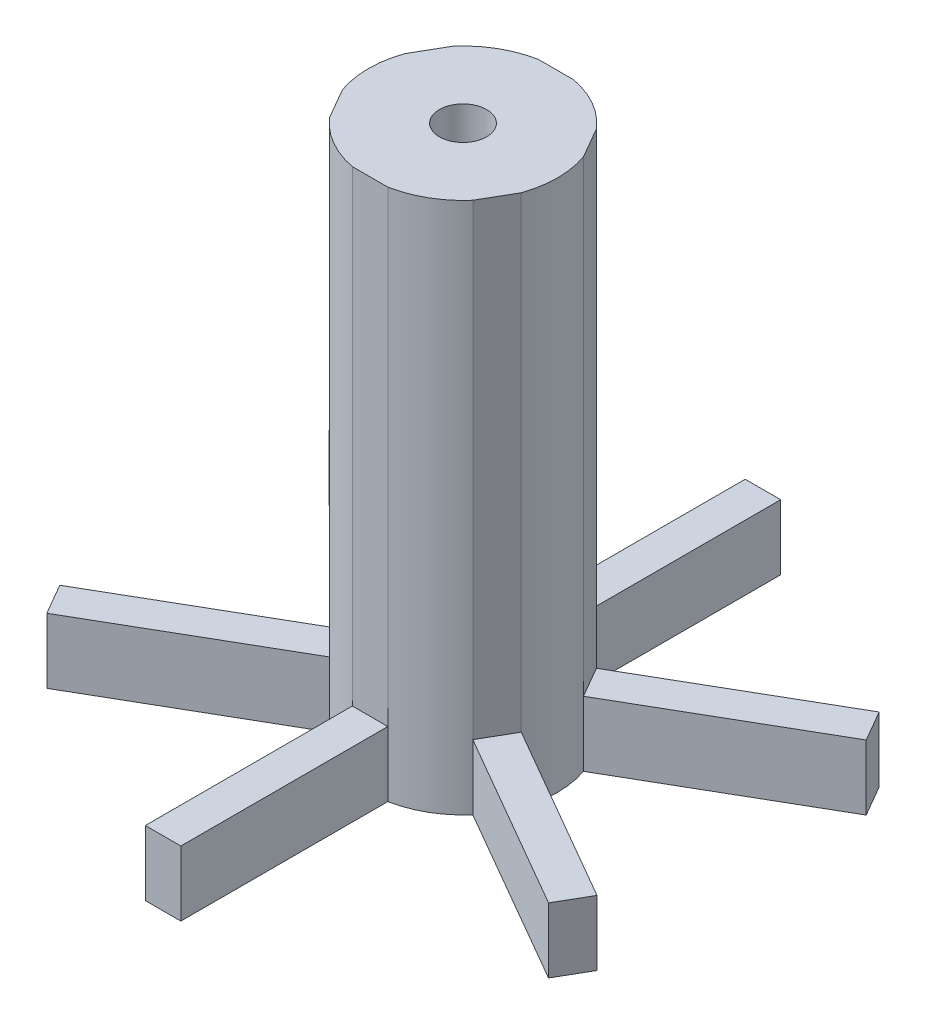
SolidWorks part; units mm, degrees
ref_plane "Front Plane" through (0, 0, 0) normal (0, 0, 1) x (1, 0, 0)
ref_plane "Top Plane" through (0, 0, 0) normal (0, 1, 0) x (1, 0, 0)
ref_plane "Right Plane" through (0, 0, 0) normal (1, 0, 0) x (0, 0, -1)
sketch "Sketch1" plane through (0, 0, 0) normal (0, 1, 0) x (1, 0, 0)
  line L24 (-1.5, -7.8581) -> (1.5, -7.8581)
  line L25 (1.5, -7.8581) -> (1.5, -25.3581)
  line L26 (1.5, -25.3581) -> (-1.5, -25.3581)
  line L27 (-1.5, -25.3581) -> (-1.5, -7.8581)
  line L28 (-22.7108, -11.38) -> (-7.5553, -2.63)
  line L29 (-7.5553, -2.63) -> (-6.0553, -5.2281)
  line L30 (-6.0553, -5.2281) -> (-21.2108, -13.9781)
  line L31 (-21.2108, -13.9781) -> (-22.7108, -11.38)
  line L32 (-21.2108, 13.9781) -> (-6.0553, 5.2281)
  line L33 (-6.0553, 5.2281) -> (-7.5553, 2.63)
  line L34 (-7.5553, 2.63) -> (-22.7108, 11.38)
  line L35 (-22.7108, 11.38) -> (-21.2108, 13.9781)
  line L36 (1.5, 25.3581) -> (1.5, 7.8581)
  line L37 (1.5, 7.8581) -> (-1.5, 7.8581)
  line L38 (-1.5, 7.8581) -> (-1.5, 25.3581)
  line L39 (-1.5, 25.3581) -> (1.5, 25.3581)
  line L40 (22.7108, 11.38) -> (7.5553, 2.63)
  line L41 (7.5553, 2.63) -> (6.0553, 5.2281)
  line L42 (6.0553, 5.2281) -> (21.2108, 13.9781)
  line L43 (21.2108, 13.9781) -> (22.7108, 11.38)
  line L44 (21.2108, -13.9781) -> (6.0553, -5.2281)
  line L45 (6.0553, -5.2281) -> (7.5553, -2.63)
  line L46 (7.5553, -2.63) -> (22.7108, -11.38)
  line L47 (22.7108, -11.38) -> (21.2108, -13.9781)
  arc A0 (1.5, -7.8581) -> (6.0553, -5.2281) centre (0, 0) ccw
  circle A1 centre (0, 0) radius 2
  arc A2 (-6.0553, -5.2281) -> (-1.5, -7.8581) centre (0, 0) ccw
  arc A3 (7.5553, -2.63) -> (7.5553, 2.63) centre (0, 0) ccw
  arc A4 (6.0553, 5.2281) -> (1.5, 7.8581) centre (0, 0) ccw
  arc A5 (-1.5, 7.8581) -> (-6.0553, 5.2281) centre (0, 0) ccw
  arc A6 (-7.5553, 2.63) -> (-7.5553, -2.63) centre (0, 0) ccw
  point P7 (0, -7.8581)
  point P31 (0, 0)
  point P32 (0, 0)
  dimension "D1" = 4
  dimension "D2" = 16
  dimension "D3" = 3
  dimension "D4" = 17.5
  dimension "D5" = 6
extrude "Boss-Extrude1" add sketch "Sketch1" along normal blind 45 contours A0 L47 L43 L39 L35 A1 region at (-3.8879, 0, 6.734)
extrude "Boss-Extrude2" add sketch "Sketch1<3>" along normal blind 5.5 contours A0 L25 | A0 L46 L45 L44 | A0 L42 L41 L40 | A0 L38 L37 L36 | L32 L35 L34 L33 | L30 L31 L28 L29 | L36 L37 L38 L39 | L40 L41 L42 L43 | L27 L24 L25 L26 | L44 L45 L46 L47 region at (0, 0, 16.6081) region at (14.3831, 0, 8.3041) region at (14.3831, 0, -8.3041) region at (0, 0, -16.6081)
sketch "Sketch1<3>" plane through (0, 0, 0) normal (0, 1, 0) x (1, 0, 0) same geometry as "Sketch1"
